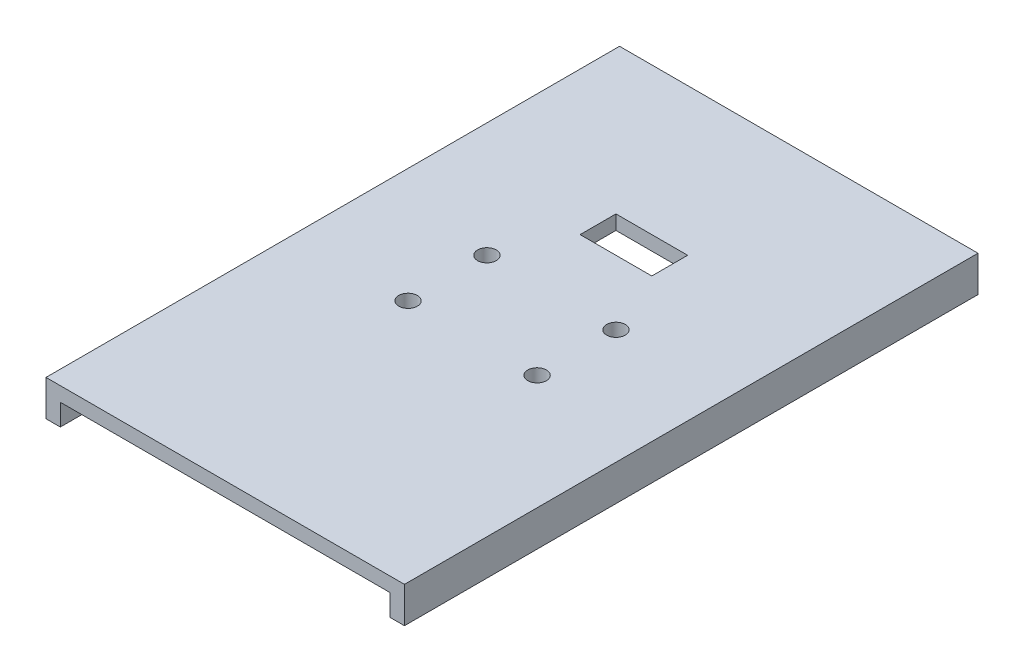
SolidWorks part; units mm, degrees
ref_plane "Front Plane" through (0, 0, 0) normal (0, 0, 1) x (1, 0, 0)
ref_plane "Top Plane" through (0, 0, 0) normal (0, 1, 0) x (1, 0, 0)
ref_plane "Right Plane" through (0, 0, 0) normal (1, 0, 0) x (0, 0, -1)
sketch "Sketch1" plane through (0, 0, 0) normal (0, 1, 0) x (1, 0, 0)
  line L1 (0, 0) -> (40, 0)
  line L2 (0, 0) -> (0, 80)
  line L3 (0, 80) -> (40, 80)
  line L4 (40, 0) -> (40, 80)
  dimension "D1" = 40
  dimension "D2" = 80
extrude "Boss-Extrude1" add sketch "Sketch1" along normal blind 2
sketch "Sketch2" plane through (0, 0, 0) normal (0, 0, 1) x (1, 0, 0)
  line L0 (0, 2) -> (-5, 2)
  line L1 (-5, 2) -> (-5, -3)
  line L2 (-5, -3) -> (-3, -3)
  line L3 (-3, -3) -> (-3, 0)
  line L4 (-3, 0) -> (0, 0)
  line L5 (0, 0) -> (0, 2)
  line L6 (20, 0) -> (20, 12.7492) construction
  line L8 (0, 0) -> (40, 0) construction
  line L9 (43, 0) -> (40, 0)
  line L10 (43, -3) -> (43, 0)
  line L11 (45, -3) -> (43, -3)
  line L12 (45, 2) -> (45, -3)
  line L13 (40, 2) -> (45, 2)
  line L14 (40, 0) -> (40, 2)
  point P11 (20, 0)
  dimension "D1" = 2
  dimension "D2" = 5
  dimension "D3" = 5
extrude "Boss-Extrude2" add sketch "Sketch2" against normal up to vertex (80 mm away) up to point (0, 2, -80)
sketch "Sketch3" plane through (0, 2, 0) normal (0, 1, 0) x (1, 0, 0)
  line L0 (20, 0) -> (20, 81.8773) construction
  line L1 (-5, 80) -> (-5, 0) construction
  line L3 (-5, 0) -> (45, 0) construction
  line L4 (-5, 40) -> (58.6355, 40) construction
  line L6 (15, 59.5) -> (25, 59.5)
  line L7 (15, 59.5) -> (15, 54.5)
  line L8 (15, 54.5) -> (25, 54.5)
  line L9 (25, 59.5) -> (25, 54.5)
  circle A0 centre (11, 45.5) radius 1.3
  circle A3 centre (11, 34.5) radius 1.3
  circle A4 centre (29, 45.5) radius 1.3
  circle A5 centre (29, 34.5) radius 1.3
  point P3 (20, 40.9387)
  point P5 (20, 0)
  point P9 (-5, 40)
  point P19 (25, 57)
  point P24 (20, 54.5)
  dimension "D1" = 2.6
  dimension "D4" = 9
  dimension "D2" = 5.5
  dimension "D3" = 11
  dimension "D5" = 5
  dimension "D6" = 10
  dimension "D7" = 17
extrude "Cut-Extrude1" cut sketch "Sketch3" against normal blind 2
